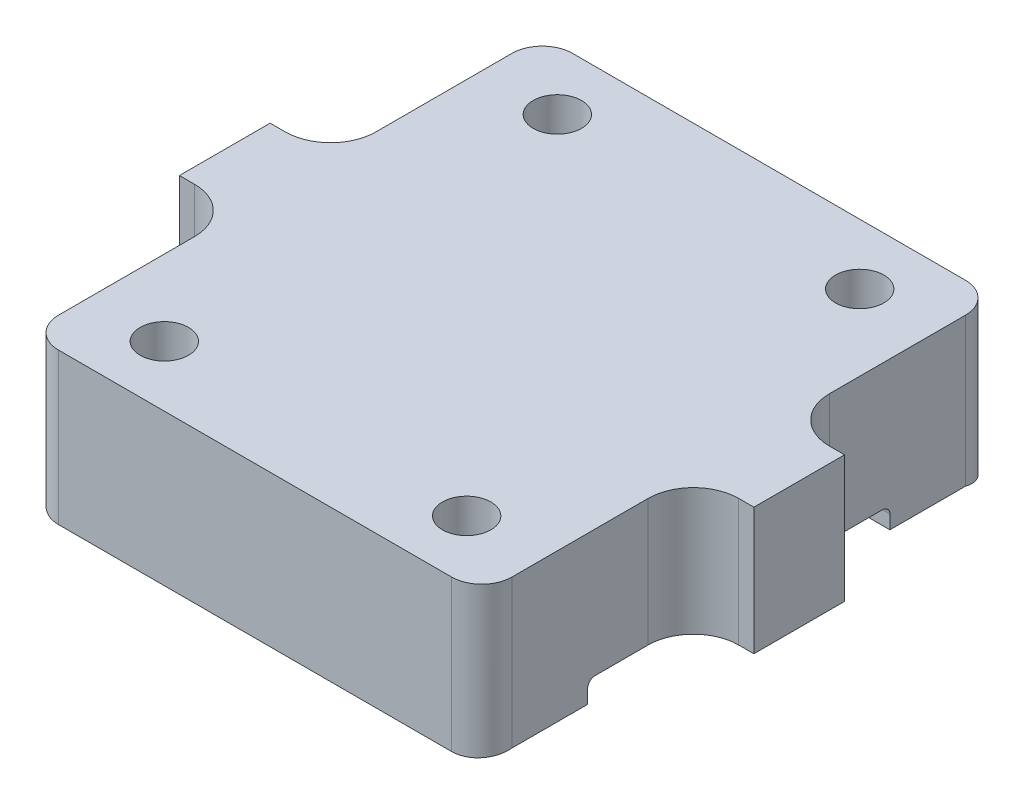
SolidWorks part; units mm, degrees
material "ABS"
ref_plane "Front" through (0, 0, 0) normal (0, 0, 1) x (1, 0, 0)
ref_plane "Top" through (0, 0, 0) normal (0, 1, 0) x (1, 0, 0)
ref_plane "Right" through (0, 0, 0) normal (1, 0, 0) x (0, 0, -1)
sketch "Szkic1" plane through (0, 0, 0) normal (1, 0, 0) x (0, 0, -1)
  line L26 (10, -5.5) -> (15, -5.5)
  line L27 (0, 4.3) -> (17, 4.3)
  line L30 (17, 4.3) -> (17, -6)
  line L31 (10, -5.5) -> (10, -4.6)
  line L32 (0, -4.1) -> (9.5, -4.1)
  line L33 (-10, -5.5) -> (-10, -4.6)
  line L34 (-17, 4.3) -> (-17, -5.7)
  line L35 (-10, -5.5) -> (-15, -5.5)
  line L38 (0, -4.1) -> (-9.5, -4.1)
  line L40 (0, 4.3) -> (-17, 4.3)
  line L46 (15, -5.5) -> (17, -6)
  line L47 (-15, -5.5) -> (-17, -5.7)
  arc A16 (10, -4.6) -> (9.5, -4.1) centre (9.5, -4.6) ccw
  arc A17 (-9.5, -4.1) -> (-10, -4.6) centre (-9.5, -4.6) ccw
  dimension "D1" = 1.4
  dimension "D2" = 10
  dimension "D3" = 0.2
  dimension "D4" = 10
extrude "Dodanie-wyciągnięcie1" add sketch "Szkic1" along normal blind 38
sketch "Szkic3" plane through (0, 4.3, 0) normal (0, 1, 0) x (1, 0, 0)
  line L1 (0, -17) -> (4, -17)
  line L2 (0, -17) -> (0, -3)
  line L3 (0, -3) -> (4, -3)
  line L4 (4, -17) -> (4, -3)
  line L5 (0, 17) -> (4, 17)
  line L6 (0, 17) -> (0, 3)
  line L7 (0, 3) -> (4, 3)
  line L8 (4, 17) -> (4, 3)
  line L9 (38, -17) -> (34, -17)
  line L10 (38, -17) -> (38, -3)
  line L11 (38, -3) -> (34, -3)
  line L12 (34, -17) -> (34, -3)
  line L13 (38, 17) -> (34, 17)
  line L14 (38, 17) -> (38, 3)
  line L15 (38, 3) -> (34, 3)
  line L16 (34, 17) -> (34, 3)
  dimension "D1" = 4
  dimension "D2" = 4
  dimension "D3" = 14
  dimension "D4" = 14
  dimension "D5" = 4
  dimension "D6" = 4
  dimension "D7" = 14
  dimension "D8" = 14
extrude "Wytnij-wyciągnięcie1" cut sketch "Szkic3" against normal through all
fillet "Zaokrąglenie1" radius 3 4 edges at (34, 0.1, -3) (34, 0.1, 3) (4, 0.1, -3) (4, 0.1, 3)
sketch "Szkic4" plane through (0, 4.3, 0) normal (0, 1, 0) x (1, 0, 0)
  line L0 (4, 6) -> (4, 17) construction
  line L1 (34, 17) -> (4, 17) construction
  line L2 (34, 17) -> (34, 6) construction
  line L3 (4, -17) -> (4, -6) construction
  line L4 (34, -6) -> (34, -17) construction
  line L5 (34, -17) -> (4, -17) construction
  circle A0 centre (9, 13) radius 1.6
  circle A1 centre (29, 13) radius 1.6
  circle A2 centre (9, -13) radius 1.6
  circle A3 centre (29, -13) radius 1.6
  dimension "D1" = 5
  dimension "D9" = 3.2
  dimension "D10" = 3.2
  dimension "D11" = 3.2
  dimension "D12" = 3.2
  dimension "D2" = 4
  dimension "D3" = 5
  dimension "D4" = 4
  dimension "D5" = 5
  dimension "D6" = 5
  dimension "D7" = 4
  dimension "D8" = 4
extrude "Wytnij-wyciągnięcie2" cut sketch "Szkic4" against normal through all
fillet "Zaokrąglenie2" radius 2 4 edges at (34, -0.7, 17) (34, -0.85, -17) (4, -0.85, -17) (4, -0.7, 17)
